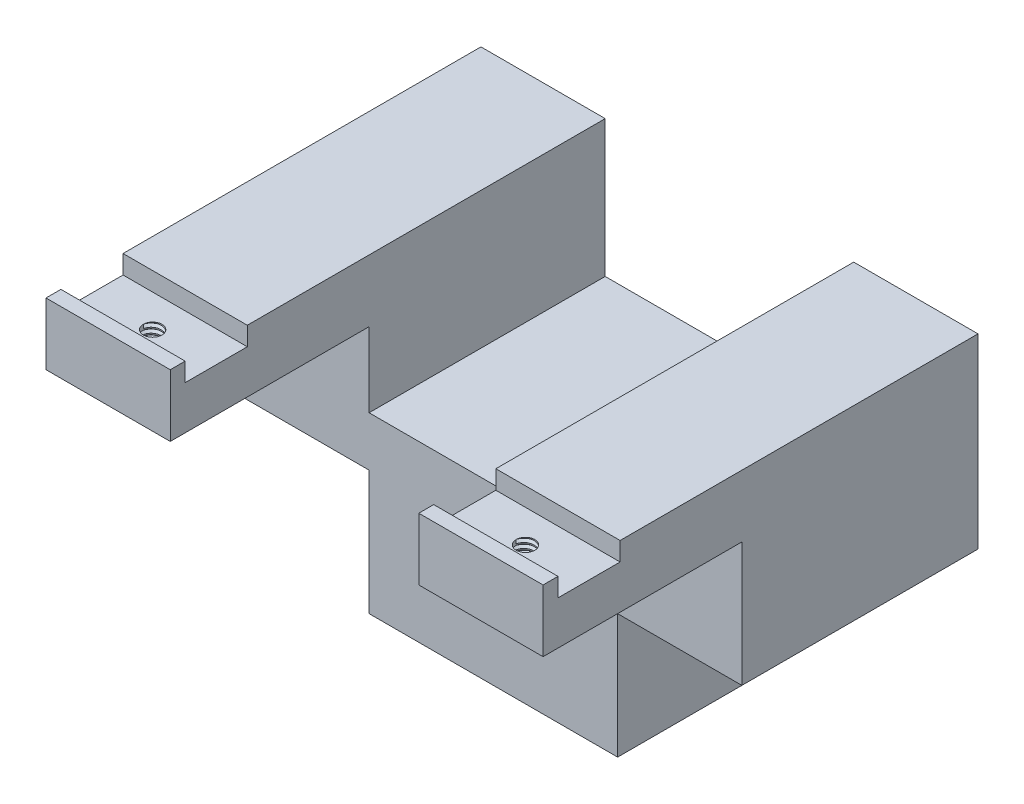
SolidWorks part; units mm, degrees
ref_plane "Front Plane" through (0, 0, 0) normal (0, 0, 1) x (1, 0, 0)
ref_plane "Top Plane" through (0, 0, 0) normal (0, 1, 0) x (1, 0, 0)
ref_plane "Right Plane" through (0, 0, 0) normal (1, 0, 0) x (0, 0, -1)
sketch "Sketch1" plane through (0, 0, 0) normal (0, 1, 0) x (1, 0, 0)
  line L1 (-50.8, -44.45) -> (50.8, -44.45)
  line L2 (-50.8, -44.45) -> (-50.8, 44.45)
  line L3 (-50.8, 44.45) -> (50.8, 44.45)
  line L4 (50.8, -44.45) -> (50.8, 44.45)
  line L5 (-50.8, -44.45) -> (50.8, 44.45) construction
  line L6 (-50.8, 44.45) -> (50.8, -44.45) construction
  point P0 (0, 0)
  dimension "D1" = 101.6
  dimension "D2" = 88.9
extrude "Boss-Extrude1" add sketch "Sketch1" along normal blind 63.5
sketch "Sketch2" plane through (50.8, 0, 0) normal (1, 0, 0) x (0, 0, -1)
  line L1 (-44.45, 0) -> (-3.81, 0)
  line L2 (-44.45, 0) -> (-44.45, 25.4)
  line L3 (-44.45, 25.4) -> (-3.81, 25.4)
  line L4 (-3.81, 0) -> (-3.81, 25.4)
  dimension "D1" = 40.64
  dimension "D2" = 25.4
extrude "Cut-Extrude1" cut sketch "Sketch2" against normal blind 101.6
sketch "Sketch3" plane through (50.8, 0, 0) normal (1, 0, 0) x (0, 0, -1)
  line L0 (-44.45, 63.5) -> (44.45, 63.5) construction
  line L1 (-41.402, 63.5) -> (-28.702, 63.5)
  line L2 (-41.402, 63.5) -> (-41.402, 59.69)
  line L3 (-41.402, 59.69) -> (-28.702, 59.69)
  line L4 (-28.702, 63.5) -> (-28.702, 59.69)
  dimension "D1" = 3.048
  dimension "D2" = 3.81
  dimension "D3" = 12.7
extrude "Cut-Extrude2" cut sketch "Sketch3" against normal blind 101.6
sketch "Sketch5" plane through (0, 0, 44.45) normal (0, 0, 1) x (1, 0, 0)
  line L0 (-50.8, 63.5) -> (50.8, 63.5) construction
  line L1 (-25.4, 63.5) -> (25.4, 63.5)
  line L2 (-25.4, 63.5) -> (-25.4, 35.56)
  line L3 (-25.4, 35.56) -> (25.4, 35.56)
  line L4 (25.4, 63.5) -> (25.4, 35.56)
  dimension "D1" = 50.8
  dimension "D2" = 27.94
extrude "Cut-Extrude3" cut sketch "Sketch5" against normal blind 101.6
sketch "Sketch7" plane through (0, 0, -44.45) normal (0, 0, -1) x (-1, 0, 0)
  line L1 (-50.8, 0) -> (-25.4, 0)
  line L2 (-50.8, 0) -> (-50.8, 25.4)
  line L3 (-50.8, 25.4) -> (-25.4, 25.4)
  line L4 (-25.4, 0) -> (-25.4, 25.4)
  dimension "D1" = 25.4
  dimension "D2" = 25.4
extrude "Cut-Extrude4" cut sketch "Sketch7" against normal blind 101.6
sketch "Sketch8" plane through (0, 0, -44.45) normal (0, 0, -1) x (-1, 0, 0)
  line L1 (50.8, 0) -> (25.4, 0)
  line L2 (50.8, 0) -> (50.8, 25.4)
  line L3 (50.8, 25.4) -> (25.4, 25.4)
  line L4 (25.4, 0) -> (25.4, 25.4)
  dimension "D1" = 25.4
  dimension "D2" = 25.4
extrude "Cut-Extrude5" cut sketch "Sketch8" against normal blind 101.6
sketch "Sketch9" plane through (50.8, 0, 0) normal (1, 0, 0) x (0, 0, -1)
  line L1 (-44.45, 25.4) -> (-3.81, 25.4)
  line L2 (-44.45, 25.4) -> (-44.45, 50.8)
  line L3 (-44.45, 50.8) -> (-3.81, 50.8)
  line L4 (-3.81, 25.4) -> (-3.81, 50.8)
  dimension "D1" = 40.64
  dimension "D2" = 25.4
extrude "Cut-Extrude6" cut sketch "Sketch9" against normal blind 101.6
sketch "Sketch10" plane through (0, 59.69, 0) normal (0, 1, 0) x (1, 0, 0)
  line L0 (-25.4, -41.402) -> (-25.4, -28.702) construction
  line L1 (0, -34.925) -> (0, 34.925) construction
  circle A0 centre (-38.1, -35.3478) radius 1.905
  circle A1 centre (38.1, -35.3478) radius 1.905
  point P4 (-25.4, -35.052)
  dimension "D1" = 12.7
extrude "Cut-Extrude7" cut sketch "Sketch10" against normal blind 12.7
thread "Thread1" pitch 1.0583 start angle 0, offset 0, length 10, pitch 1.0583, diameter 3.81
ref_plane "Plane1" through (-40.005, 59.69, 35.3478) normal (0, 0, 1) x (-1, 0, 0)
sketch "Thread Profile1" plane through (-40.005, 59.69, 35.3478) normal (0, 0, 1) x (-1, 0, 0)
  line L0 (0, 0) -> (0, 1.0583) construction
  line L1 (0, 0) -> (0.5728, 0.3307)
  line L2 (0.5728, 0.3307) -> (0.5728, 0.463)
  line L3 (0.5728, 0.463) -> (0, 0.7937)
  line L4 (0.5728, 0.3969) -> (0, 0.3969) construction
  line L11 (0, 0) -> (0, 0.7937)
  point P2 (0, 0)
  dimension "Pitch" = 1.0583
  dimension "Profile_Angle" = 60
  dimension "Profile_Land" = 0.1323
  dimension "Profile_Height" = 0.5728
thread "Thread2" pitch 1.0583 profile "Thread Profile2" start angle 0, offset 0, length 10, pitch 1.0583, diameter 3.81
ref_plane "Plane2" through (36.195, 59.69, 35.3478) normal (0, 0, 1) x (-1, 0, 0)
sketch "Thread Profile2" plane through (36.195, 59.69, 35.3478) normal (0, 0, 1) x (-1, 0, 0)
  line L0 (0, 0) -> (0, 1.0583) construction
  line L1 (0, 0) -> (0.5728, 0.3307)
  line L2 (0.5728, 0.3307) -> (0.5728, 0.463)
  line L3 (0.5728, 0.463) -> (0, 0.7937)
  line L4 (0.5728, 0.3969) -> (0, 0.3969) construction
  line L11 (0, 0) -> (0, 0.7937)
  point P2 (0, 0)
  dimension "Pitch" = 1.0583
  dimension "Profile_Angle" = 60
  dimension "Profile_Land" = 0.1323
  dimension "Profile_Height" = 0.5728
sketch "Sketch17" plane through (0, 0, 0) normal (0, -1, 0) x (1, 0, 0)
  circle A0 centre (0, -20.32) radius 3.175
extrude "Cut-Extrude8" cut sketch "Sketch17" against normal blind 19.05
thread "Thread3" pitch 1.27 profile "Thread Profile3" start angle 0, offset 0, length 10, pitch 1.27, diameter 6.35
ref_plane "Plane3" through (3.175, 0, -20.32) normal (0, 0, 1) x (1, 0, 0)
sketch "Thread Profile3" plane through (3.175, 0, -20.32) normal (0, 0, 1) x (1, 0, 0)
  line L0 (0, 0) -> (0, 1.27) construction
  line L1 (0, 0) -> (0.6874, 0.3969)
  line L2 (0.6874, 0.3969) -> (0.6874, 0.5556)
  line L3 (0.6874, 0.5556) -> (0, 0.9525)
  line L4 (0.6874, 0.4762) -> (0, 0.4762) construction
  line L11 (0, 0) -> (0, 0.9525)
  point P2 (0, 0)
  dimension "Pitch" = 1.27
  dimension "Profile_Angle" = 60
  dimension "Profile_Land" = 0.1588
  dimension "Profile_Height" = 0.6874
